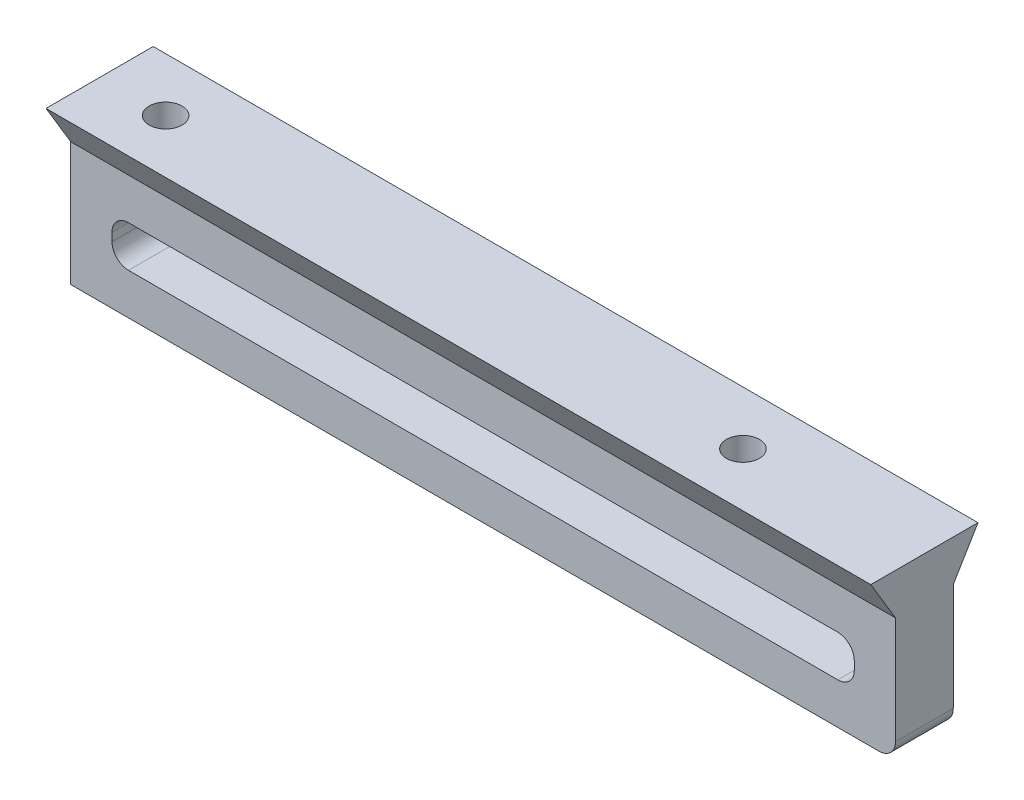
SolidWorks part; units mm, degrees
ref_plane "Front Plane" through (0, 0, 0) normal (0, 0, 1) x (1, 0, 0)
ref_plane "Top Plane" through (0, 0, 0) normal (0, 1, 0) x (1, 0, 0)
ref_plane "Right Plane" through (0, 0, 0) normal (1, 0, 0) x (0, 0, -1)
sketch "Sketch1" plane through (0, 0, 0) normal (0, 1, 0) x (1, 0, 0)
  line L1 (-50, 3.5) -> (50, 3.5)
  line L2 (-50, 3.5) -> (-50, -3.5)
  line L3 (-50, -3.5) -> (50, -3.5)
  line L4 (50, 3.5) -> (50, -3.5)
  line L5 (-50, 3.5) -> (50, -3.5) construction
  line L6 (-50, -3.5) -> (50, 3.5) construction
  point P0 (0, 0)
  dimension "D1" = 100
  dimension "D2" = 7
extrude "Boss-Extrude1" add sketch "Sketch1" along normal blind 20
sketch "Sketch2" plane through (0, 20, 0) normal (0, 1, 0) x (1, 0, 0)
  circle A0 centre (-42, 0) radius 2
  circle A1 centre (28, 0) radius 2
  dimension "D2" = 4
  dimension "D3" = 4
  dimension "D1" = 70
  dimension "D4" = 28
extrude "Cut-Extrude1" cut sketch "Sketch2" against normal blind 10
sketch "Sketch4" plane through (-50, 0, 0) normal (-1, 0, 0) x (0, 0, 1)
  line L0 (-3.5, 15) -> (-3.5, 20)
  line L1 (-3.5, 20) -> (-3.5, 0) construction
  line L2 (-3.5, 20) -> (-6.5, 20)
  line L3 (-6.5, 20) -> (-3.5, 15)
  line L4 (3.5, 20) -> (6.5, 20)
  line L5 (6.5, 20) -> (3.5, 15)
  line L6 (3.5, 20) -> (3.5, 0) construction
  line L7 (3.5, 20) -> (3.5, 15)
  dimension "D1" = 3
  dimension "D2" = 3
  dimension "D3" = 5
  dimension "D4" = 5
extrude "Boss-Extrude2" add sketch "Sketch4" against normal up to surface (100 mm away) up to face at (50, 10, 0)
ref_plane "Plane1" through (-25, 25, 0) normal (-0.7071, 0.7071, 0) x (0.7071, 0.7071, 0)
sketch "Sketch8" plane through (0, 0, -3.5) normal (0, 0, -1) x (-1, 0, 0)
  line L0 (-50, 15) -> (-50, 0) construction
  line L1 (-45, 10) -> (45, 10)
  line L2 (-45, 10) -> (-45, 5)
  line L3 (-45, 5) -> (45, 5)
  line L4 (45, 10) -> (45, 5)
  line L5 (-50, 15) -> (50, 15) construction
  line L6 (-50, 0) -> (50, 0) construction
  line L7 (50, 15) -> (50, 0) construction
  dimension "D1" = 5
  dimension "D2" = 5
  dimension "D3" = 5
  dimension "D4" = 5
extrude "Cut-Extrude5" cut sketch "Sketch8" against normal blind 10
fillet "Fillet2" radius 2 4 edges at (45, 10, 0) (45, 5, 0) (-45, 5, 0) (-45, 10, 0)
fillet "Fillet3" radius 2 1 edges at (50, 0, 0)
